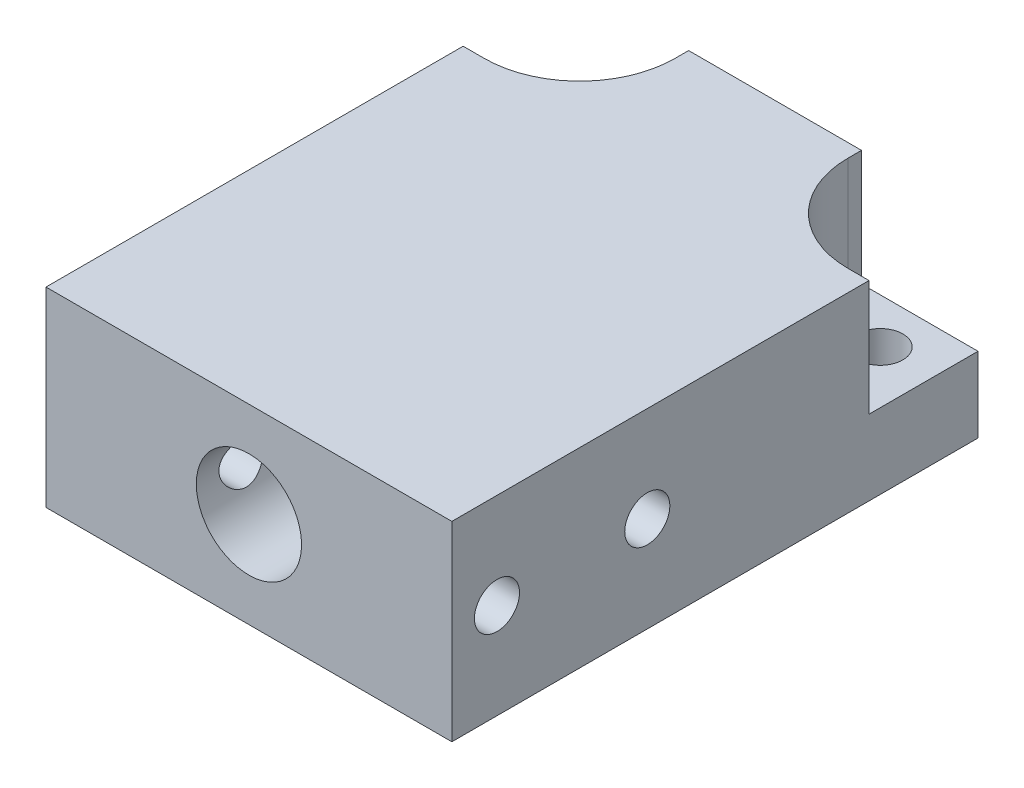
SolidWorks part; units mm, degrees
material "6061 Alloy"
ref_plane "Front Plane" through (0, 0, 0) normal (0, 0, 1) x (1, 0, 0)
ref_plane "Top Plane" through (0, 0, 0) normal (0, 1, 0) x (1, 0, 0)
ref_plane "Right Plane" through (0, 0, 0) normal (1, 0, 0) x (0, 0, -1)
sketch "Sketch1" plane through (0, 0, 0) normal (0, 1, 0) x (1, 0, 0)
  line L1 (-13.5, -17.5) -> (13.5, -17.5)
  line L2 (-13.5, -17.5) -> (-13.5, 17.5)
  line L3 (-13.5, 17.5) -> (13.5, 17.5)
  line L4 (13.5, -17.5) -> (13.5, 17.5)
  line L5 (-13.5, -17.5) -> (13.5, 17.5) construction
  line L6 (-13.5, 17.5) -> (13.5, -17.5) construction
  point P0 (0, 0)
  dimension "D1" = 27
  dimension "D2" = 35
extrude "Boss-Extrude1" add sketch "Sketch1" along normal mid plane 12.7 contours L1 L4 L3 L2
sketch "Sketch2" plane through (0, 0, -17.5) normal (0, 0, -1) x (-1, 0, 0)
  circle A0 centre (0, 0) radius 3.5
  dimension "D1" = 7
extrude "Cut-Extrude1" cut sketch "Sketch2" against normal through all both and the other way through all
sketch "Sketch3" plane through (13.5, 0, 0) normal (1, 0, 0) x (0, 0, -1)
  line L0 (-17.5, 0) -> (-2.5, 0) construction
  line L1 (-17.5, 6.35) -> (-17.5, -6.35) construction
  line L2 (-4.5, 0) -> (-14.5, 0) construction
  circle A0 centre (-4.5, 0) radius 1.5
  circle A1 centre (-14.5, 0) radius 1.5
  dimension "D2" = 3
  dimension "D1" = 15
  dimension "D3" = 10
  dimension "D4" = 3
extrude "Cut-Extrude2" cut sketch "Sketch3" against normal through all both and the other way through all
sketch "Sketch4" plane through (0, 6.35, 0) normal (0, 1, 0) x (1, 0, 0)
  line L0 (-10, 14.5) -> (10, 14.5) construction
  line L1 (-13.5, 17.5) -> (13.5, 17.5) construction
  circle A0 centre (-10, 14.5) radius 1.5
  circle A1 centre (10, 14.5) radius 1.5
  point P2 (0, 14.5)
  dimension "D2" = 3
  dimension "D1" = 20
  dimension "D3" = 3
extrude "Cut-Extrude3" cut sketch "Sketch4" against normal through all both and the other way through all
sketch "Sketch9" plane through (0, 0, -17.5) normal (0, 0, -1) x (-1, 0, 0)
  point P0 (0, 0)
hole_wizard "Tap Drill for M10x1.0 Tap1" positions "3DSketch4" profile "Sketch10" hole size "M10x1.0" standard "ANSI Metric"
sketch3d "3DSketch4"
  point P0 (0, 0, -17.5)
  point P3 (0, 0, -17.5)
sketch "Sketch10" plane through (0, 0, -17.5) normal (1, 0, 0) x (0, 1, 0)
  line L0 (0, 0) -> (0, 8.7039)
  line L1 (0, 8.7039) -> (4.5, 6)
  line L2 (4.5, 6) -> (4.5, 0)
  line L5 (4.5, 0) -> (0, 0)
  line L10 (0, 8.7039) -> (-4.5, 6) construction
  line L11 (0, -6.35) -> (0, 107.95) construction
  dimension "Hole Dia." = 9
  dimension "Hole Depth" = 6
  dimension "Drill Angle" = 118
sketch "Sketch11" plane through (0, 6.35, 0) normal (0, 1, 0) x (1, 0, 0)
  line L0 (0, -6.985) -> (0, 6.985) construction
  line L1 (-13.5, 17.5) -> (-5.75, 17.5)
  line L2 (-13.5, 17.5) -> (-13.5, 10.25)
  line L3 (-13.5, 10.25) -> (-5.75, 10.25)
  line L4 (-5.75, 17.5) -> (-5.75, 10.25)
  line L5 (5.75, 17.5) -> (5.75, 10.25)
  line L6 (13.5, 17.5) -> (5.75, 17.5)
  line L7 (13.5, 17.5) -> (13.5, 10.25)
  line L8 (13.5, 10.25) -> (5.75, 10.25)
  circle A0 centre (-10, 14.5) radius 4.25 construction
  circle A1 centre (-10, 14.5) radius 1.5 construction
  dimension "D1" = 8.5
extrude "Cut-Extrude4" cut sketch "Sketch11" against normal offset from surface (7.7 mm away) 5 up to face at (-10, -6.35, -13)
fillet "Fillet3" radius 6.35 2 edges at (5.75, 2.5, -10.25) (-5.75, 2.5, -10.25)
